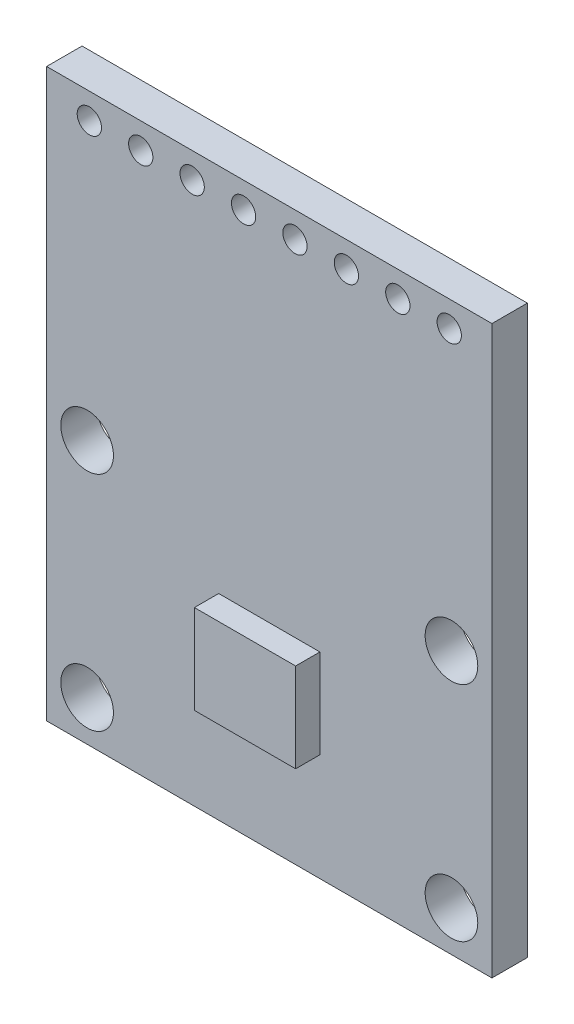
SolidWorks part; units mm, degrees
ref_plane "Front Plane" through (0, 0, 0) normal (0, 0, 1) x (1, 0, 0)
ref_plane "Top Plane" through (0, 0, 0) normal (0, 1, 0) x (1, 0, 0)
ref_plane "Right Plane" through (0, 0, 0) normal (1, 0, 0) x (0, 0, -1)
sketch "Sketch1" plane through (0, 0, 0) normal (0, 0, 1) x (1, 0, 0)
  line L1 (-11, -14) -> (11, -14)
  line L2 (-11, -14) -> (-11, 14)
  line L3 (-11, 14) -> (11, 14)
  line L4 (11, -14) -> (11, 14)
  line L5 (-11, -14) -> (11, 14) construction
  line L6 (-11, 14) -> (11, -14) construction
  point P0 (0, 0)
  dimension "D1" = 22
  dimension "D2" = 28
extrude "Boss-Extrude1" add sketch "Sketch1" along normal blind 1.75
sketch "Sketch2" plane through (0, 0, 1.75) normal (0, 0, 1) x (1, 0, 0)
  line L0 (0, -1000) -> (0, 49000) construction
  line L1 (-1000, -6.5) -> (49000, -6.5) construction
  line L3 (-9, -12) -> (9, -12) construction
  line L4 (-9, -12) -> (-9, -1) construction
  line L5 (-9, -1) -> (9, -1) construction
  line L6 (9, -12) -> (9, -1) construction
  line L7 (-9, -12) -> (9, -1) construction
  line L8 (-9, -1) -> (9, -12) construction
  circle A0 centre (-9, -1) radius 1.3
  circle A1 centre (-9, -12) radius 1.3
  circle A2 centre (9, -12) radius 1.3
  circle A3 centre (9, -1) radius 1.3
  circle A4 centre (0, -6.5) radius 1
  point P4 (0, -6.5)
  dimension "D4" = 2.6
  dimension "D5" = 2.6
  dimension "D6" = 2.6
  dimension "D7" = 2.6
  dimension "D8" = 2
  dimension "D1" = 6.5
  dimension "D2" = 18
  dimension "D3" = 11
extrude "Cut-Extrude1" cut sketch "Sketch2" against normal through all
sketch "Sketch3" plane through (0, 0, 1.75) normal (0, 0, 1) x (1, 0, 0)
  line L0 (11, 14) -> (-11, 14) construction
  circle A0 centre (-1.27, 12.73) radius 0.6
  dimension "D1" = 1.27
  dimension "D2" = 1.27
extrude "Cut-Extrude2" cut sketch "Sketch3" against normal through all
pattern_linear "LPattern1" count 4 spacing 2.54 along (-1, 0, 0) of "Cut-Extrude2"
mirror "Mirror1" about plane through (0, 0, 0) normal (1, 0, 0) of "LPattern1"
sketch "Sketch4" plane through (0, 0, 1.75) normal (0, 0, 1) x (1, 0, 0)
  line L1 (-2.5, -8.7) -> (2.5, -8.7)
  line L2 (-2.5, -8.7) -> (-2.5, -4.3)
  line L3 (-2.5, -4.3) -> (2.5, -4.3)
  line L4 (2.5, -8.7) -> (2.5, -4.3)
  line L5 (-2.5, -8.7) -> (2.5, -4.3) construction
  line L6 (-2.5, -4.3) -> (2.5, -8.7) construction
  point P0 (0, -6.5)
  dimension "D1" = 5
  dimension "D2" = 4.4
extrude "Boss-Extrude2" add sketch "Sketch4" along normal blind 1.2
